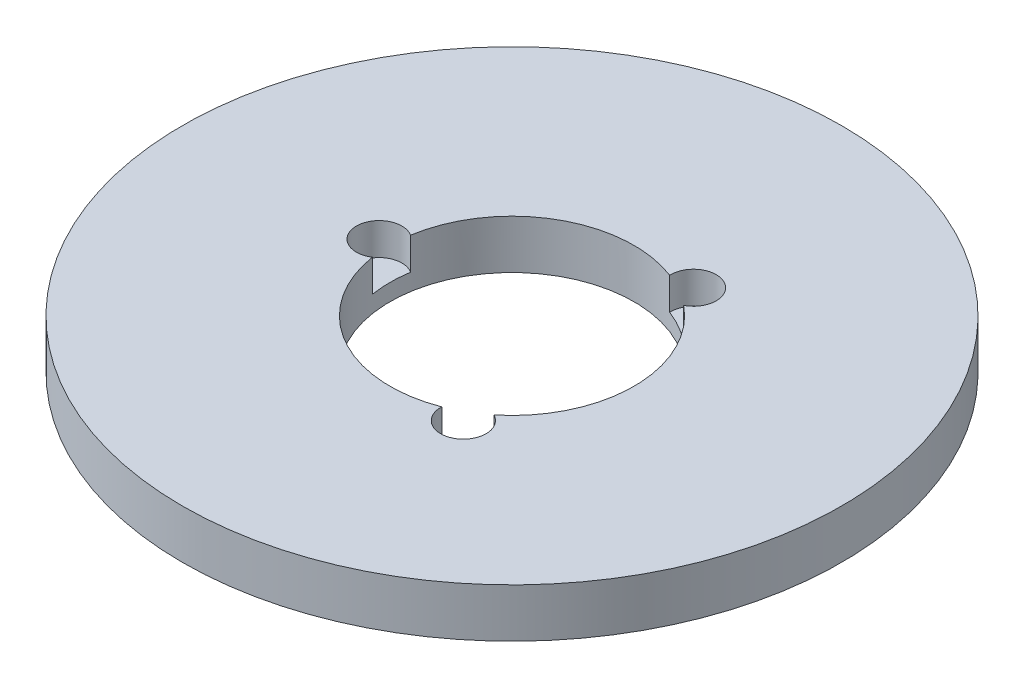
SolidWorks part; units mm, degrees
ref_plane "Front Plane" through (0, 0, 0) normal (0, 0, 1) x (1, 0, 0)
ref_plane "Top Plane" through (0, 0, 0) normal (0, 1, 0) x (1, 0, 0)
ref_plane "Right Plane" through (0, 0, 0) normal (1, 0, 0) x (0, 0, -1)
sketch "Sketch1" plane through (0, 0, 0) normal (0, 1, 0) x (1, 0, 0)
  circle A0 centre (0, 0) radius 67.5
  dimension "FLANGE_OD" = 135
extrude "Boss-Extrude1" add sketch "Sketch1" along normal blind 10
sketch "Sketch2" plane through (0, 0, 0) normal (0, 1, 0) x (1, 0, 0)
  circle A0 centre (0, 0) radius 25
  dimension "BORE_D" = 50
extrude "Cut-Extrude1" cut sketch "Sketch2" along normal through all
sketch "Sketch3" plane through (0, 10, 0) normal (0, 1, 0) x (1, 0, 0)
  circle A0 centre (0, 0) radius 27.2141 construction
  circle A1 centre (-27.2141, 0) radius 4.6543
  dimension "BOLT_D" = 9.3086
  dimension "BOLT_PCD" = 54.4282
extrude "Cut-Extrude2" cut sketch "Sketch3" against normal blind 6.566
pattern_circular "CirPattern1" count 3 over 360 about axis through (0, 0, 0) along (0, 1, 0) of "Cut-Extrude2"
